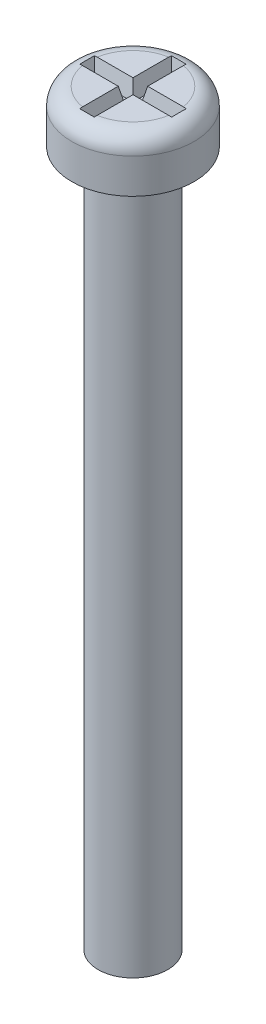
SolidWorks part; units mm, degrees
ref_plane "Спереди" through (0, 0, 0) normal (0, 0, 1) x (1, 0, 0)
ref_plane "Сверху" through (0, 0, 0) normal (0, 1, 0) x (1, 0, 0)
ref_plane "Справа" through (0, 0, 0) normal (1, 0, 0) x (0, 0, -1)
sketch "Эскиз1" plane through (0, 0, 0) normal (0, 1, 0) x (1, 0, 0)
  circle A0 centre (0, 0) radius 2
extrude "Бобышка-Вытянуть1" add sketch "Эскиз1" along normal blind 40
sketch "Эскиз2" plane through (0, 40, 0) normal (0, 1, 0) x (1, 0, 0)
  circle A0 centre (0, 0) radius 3.515
extrude "Бобышка-Вытянуть2" add sketch "Эскиз2" along normal blind 3
sketch "Эскиз3" plane through (0, 43, 0) normal (0, 1, 0) x (1, 0, 0)
  line L0 (-2.6415, 0.4228) -> (-0.4228, 0.4228)
  line L2 (-2.6415, -0.4228) -> (-2.6415, 0.4228)
  line L4 (2.6415, -0.4228) -> (2.6415, 0.4228)
  line L5 (-2.6415, -0.4228) -> (2.6415, 0.4228) construction
  line L6 (-2.6415, 0.4228) -> (2.6415, -0.4228) construction
  line L7 (-0.4228, -2.6415) -> (0.4228, -2.6415)
  line L9 (-0.4228, 2.6415) -> (0.4228, 2.6415)
  line L11 (-0.4228, -2.6415) -> (0.4228, 2.6415) construction
  line L12 (-0.4228, 2.6415) -> (0.4228, -2.6415) construction
  line L13 (-0.4228, 0.4228) -> (-0.4228, 2.6415)
  line L14 (0.4228, 2.6415) -> (0.4228, 0.4228)
  line L15 (0.4228, 0.4228) -> (2.6415, 0.4228)
  line L16 (2.6415, -0.4228) -> (0.4228, -0.4228)
  line L17 (0.4228, -0.4228) -> (0.4228, -2.6415)
  line L18 (-0.4228, -2.6415) -> (-0.4228, -0.4228)
  line L19 (-0.4228, -0.4228) -> (-2.6415, -0.4228)
  point P0 (0, 0)
  point P6 (0, 0)
extrude "Вырез-Вытянуть1" cut sketch "Эскиз3" against normal blind 1 draft 12
fillet "Скругление2" radius 1 1 edges at (0, 43, 3.515)
